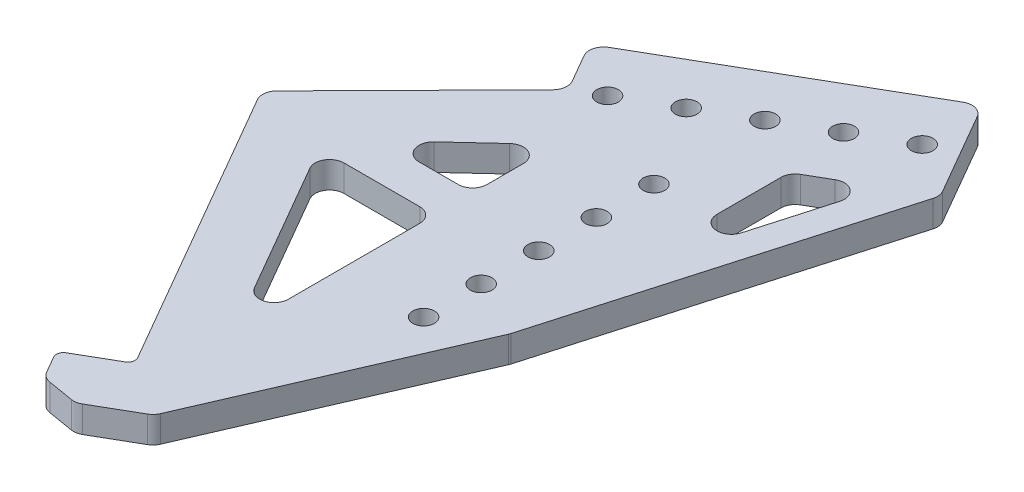
SolidWorks part; units mm, degrees
ref_plane "Front Plane" through (0, 0, 0) normal (0, 0, 1) x (1, 0, 0)
ref_plane "Top Plane" through (0, 0, 0) normal (0, 1, 0) x (1, 0, 0)
ref_plane "Right Plane" through (0, 0, 0) normal (1, 0, 0) x (0, 0, -1)
sketch "Sketch1" plane through (0, 0, 0) normal (0, 1, 0) x (1, 0, 0)
  line L0 (0, 0) -> (0, -101.6) construction
  line L1 (27.4963, 15.875) -> (-27.4963, -15.875) construction
  line L2 (25.9313, 0.3067) -> (12.7, -7.3323)
  line L3 (-11.0124, -123.6756) -> (12.6999, -68.9194)
  line L4 (-27.4963, -15.875) -> (-61.0935, -49.937)
  line L5 (25.9313, 0.3067) -> (12.7, -45.8676)
  line L6 (12.7, -45.8676) -> (12.7, -16.2776)
  line L7 (33.8463, 4.8765) -> (21.1463, 26.8735)
  line L8 (-27.4963, -15.875) -> (-33.8463, -4.8765)
  line L9 (21.1463, 26.8735) -> (-33.8463, -4.8765)
  line L10 (33.8463, 4.8765) -> (-33.8463, -4.8765) construction
  line L11 (-21.1463, -26.8735) -> (21.1463, 26.8735) construction
  line L12 (33.8463, 4.8765) -> (12.6999, -68.9194)
  line L13 (-21.1463, -26.8735) -> (-54.4806, -46.1191) construction
  line L14 (12.7, -16.2776) -> (12.7, -7.3323)
  line L15 (-61.0935, -49.937) -> (-22.9935, -115.9282)
  line L16 (-43.745, -54.5856) -> (-18.345, -98.5797)
  line L17 (-22.9935, -115.9282) -> (-33.992, -122.2782)
  line L18 (-33.992, -122.2782) -> (-30.3258, -128.6282)
  line L19 (-30.3258, -128.6282) -> (-22.0109, -130.0256)
  line L21 (-11.0124, -123.6756) -> (-22.0109, -130.0256)
  line L22 (-42.0435, -82.9326) -> (-31.045, -76.5826) construction
  line L23 (-18.345, -98.5797) -> (-18.345, -54.5856)
  line L24 (-18.345, -54.5856) -> (-43.745, -54.5856)
  line L25 (-38.2672, -46.1065) -> (-18.345, -46.1065)
  line L26 (-18.345, -46.1065) -> (-18.345, -27.6556)
  line L28 (-43.745, -54.5856) -> (-43.745, -46.1065) construction
  line L29 (-12.7, 0) -> (-12.7, -101.6) construction
  line L30 (33.8463, 4.8765) -> (-21.1463, -26.8735) construction
  line L31 (-38.2672, -46.1065) -> (-18.345, -27.6556)
  circle A0 centre (21.997, 12.7) radius 2.3813
  circle A1 centre (10.9985, 6.35) radius 2.3813
  circle A2 centre (0, 0) radius 2.3813
  circle A3 centre (-10.9985, -6.35) radius 2.3813
  circle A4 centre (-21.997, -12.7) radius 2.3813
  circle A5 centre (0, -24.4695) radius 2.3813
  circle A6 centre (0, -37.1695) radius 2.3812
  circle A7 centre (0, -49.8695) radius 2.3812
  circle A8 centre (0, -62.5695) radius 2.3813
  circle A9 centre (0, -75.2695) radius 2.3813
  point P27 (0, -68.9195)
  point P28 (27.742, 6.6257)
  point P29 (6.5957, -67.1703)
  point P53 (-12.7, -21.997)
  dimension "D4" = 4.7625
  dimension "D7" = 4.7625
  dimension "D1" = 60
  dimension "D2" = 63.5
  dimension "D3" = 101.6
  dimension "D5" = 6.35
  dimension "D8" = 24.4695
  dimension "D10" = 12.7
  dimension "D11" = 6.35
  dimension "D12" = 25.4
  dimension "D13" = 50.8
  dimension "D14" = 76.2
  dimension "D15" = 12.7
  dimension "D16" = 6.35
  dimension "D17" = 12.7
  dimension "D18" = 12.7
  dimension "D19" = 55.88
  dimension "D20" = 2
  dimension "D6" = 5
  dimension "D9" = 4
extrude "Boss-Extrude1" add sketch "Sketch1" along normal blind 5.842
fillet "Fillet1" radius 3.175 9 edges at (-18.345, 2.921, 54.5856) (-43.745, 2.921, 54.5856) (-18.345, 2.921, 98.5797) (25.9313, 2.921, -0.3067) (12.7, 2.921, 7.3323) (12.7, 2.921, 45.8676) (-18.345, 2.921, 27.6556) (-18.345, 2.921, 46.1065) (-38.2672, 2.921, 46.1065)
fillet "Fillet2" radius 3.175 5 edges at (33.8463, 2.921, -4.8765) (21.1463, 2.921, -26.8735) (-33.8463, 2.921, 4.8765) (-27.4963, 2.921, 15.875) (-61.0935, 2.921, 49.937)
fillet "Fillet3" radius 1.5875 2 edges at (-33.992, 2.921, 122.2782) (-22.9935, 2.921, 115.9282)
fillet "Fillet5" radius 3.175 4 edges at (-30.3258, 2.921, 128.6282) (-22.0109, 2.921, 130.0256) (12.6999, 2.921, 68.9194) (-11.0124, 2.921, 123.6756)
